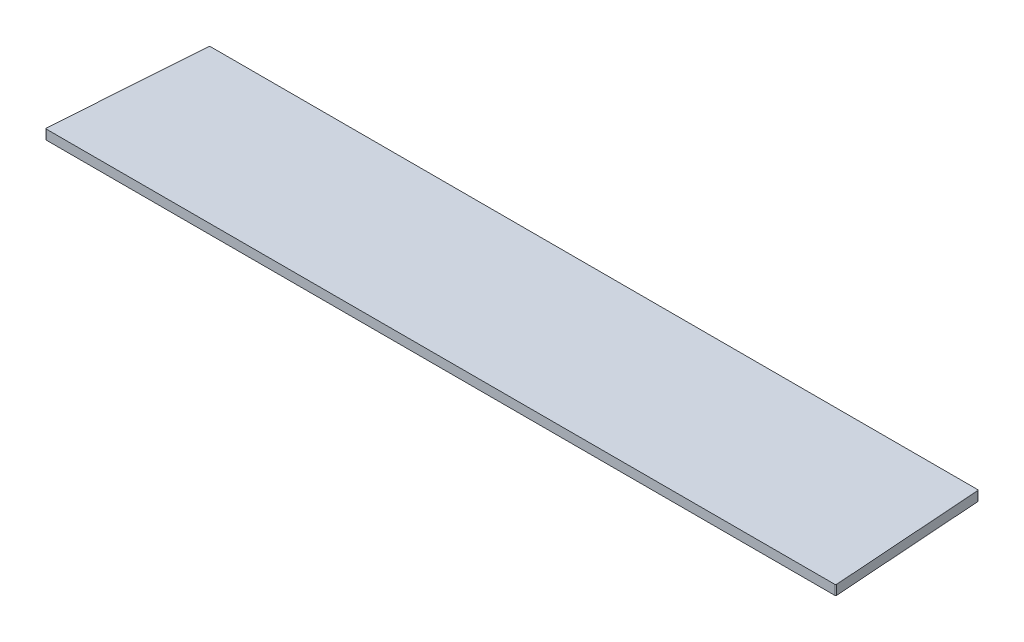
SolidWorks part; units mm, degrees
material "MS-Grade 400"
ref_plane "Front Plane" through (0, 0, 0) normal (0, 0, 1) x (1, 0, 0)
ref_plane "Top Plane" through (0, 0, 0) normal (0, 1, 0) x (1, 0, 0)
ref_plane "Right Plane" through (0, 0, 0) normal (1, 0, 0) x (0, 0, -1)
sketch "Sketch1" plane through (0, 0, 0) normal (0, 1, 0) x (1, 0, 0)
  line L0 (0, 0) -> (0, 160) construction
  line L1 (-400.8117, 160) -> (400.8117, 160)
  line L2 (-400.8117, 160) -> (-412, 0)
  line L3 (-412, 0) -> (412, 0)
  line L4 (400.8117, 160) -> (412, 0)
  dimension "D1" = 824
  dimension "D2" = 160
  dimension "D3" = 86
sheet metal parameters "Sheet-Metal1" thickness 10 parameters "D1"=92
base flange "Base-Flange1" sketch "Sketch1" thickness 10 reverse thickness direction no parameters "D1"=92
fillet "Fillet-1.0" radius 1 4 edges at (412, -5, 0) (400.8117, -5, -160) (-400.8117, -5, -160) (-412, -5, 0)
flat pattern "Flat-Pattern1" [suppressed]
sketch "Bend-Lines1" plane through (0, 0, 0) normal (0, 1, 0) x (1, 0, 0)
sketch3d "Bounding-Box1" [suppressed]
  line L0 (411.9272, 0, 0) -> (-411.9272, 0, 0) construction
  line L1 (411.9272, 160, 0) -> (-411.9272, 160, 0) construction
  line L2 (411.9272, 0, 0) -> (411.9272, 160, 0) construction
  line L3 (-411.9272, 0, 0) -> (-411.9272, 160, 0) construction
